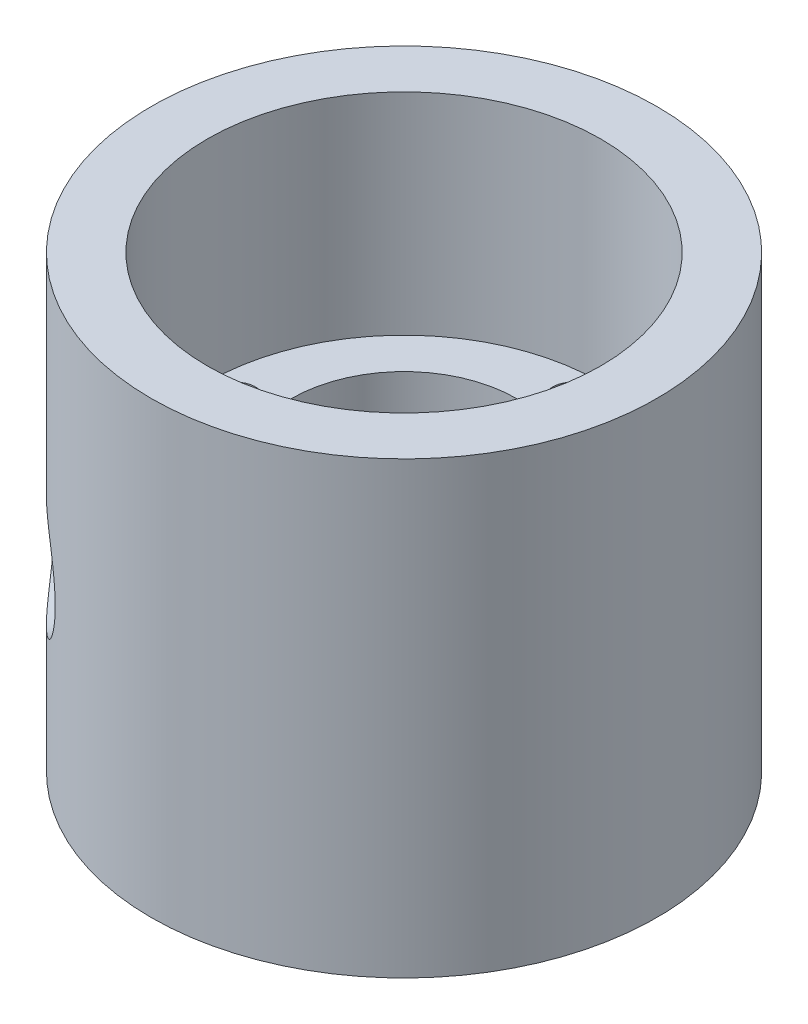
SolidWorks part; units mm, degrees
material "6061 Alloy"
ref_plane "Front Plane" through (0, 0, 0) normal (0, 0, 1) x (1, 0, 0)
ref_plane "Top Plane" through (0, 0, 0) normal (0, 1, 0) x (1, 0, 0)
ref_plane "Right Plane" through (0, 0, 0) normal (1, 0, 0) x (0, 0, -1)
sketch "Sketch1" plane through (0, 0, 0) normal (0, 1, 0) x (1, 0, 0)
  circle A1 centre (0, 0) radius 14.2875
  dimension "D2" = 28.575
extrude "Boss-Extrude1" add sketch "Sketch1" along normal blind 25.4
sketch "Sketch3" plane through (0, 0, 0) normal (0, -1, 0) x (1, 0, 0)
  circle A0 centre (0, 0) radius 11.1125
  dimension "D1" = 22.225
extrude "Cut-Extrude1" cut sketch "Sketch3" against normal blind 7.1437
sketch "Sketch4" plane through (0, 25.4, 0) normal (0, 1, 0) x (1, 0, 0)
  line L1 (-1.5875, 7.9375) -> (1.5875, 7.9375)
  line L2 (-7.9375, 1.5875) -> (-7.9375, -1.5875)
  line L3 (-1.5875, -7.9375) -> (1.5875, -7.9375)
  line L4 (7.9375, 1.5875) -> (7.9375, -1.5875)
  arc A0 (1.5875, -7.9375) -> (7.9375, -1.5875) centre (1.5875, -1.5875) ccw
  arc A1 (1.5875, 7.9375) -> (7.9375, 1.5875) centre (1.5875, 1.5875) cw
  arc A2 (-7.9375, -1.5875) -> (-1.5875, -7.9375) centre (-1.5875, -1.5875) ccw
  arc A3 (-1.5875, 7.9375) -> (-7.9375, 1.5875) centre (-1.5875, 1.5875) ccw
  point P6 (7.9375, -7.9375)
  point P9 (7.9375, 7.9375)
  point P14 (-7.9375, 7.9375)
  dimension "D3" = 6.35
  dimension "D1" = 15.875
  dimension "D2" = 15.875
  dimension "D4" = 7.9375
  dimension "D5" = 7.9375
extrude "Cut-Extrude2" cut sketch "Sketch4" against normal blind 18.2562
sketch "Sketch5" plane through (0, 25.4, 0) normal (0, 1, 0) x (1, 0, 0)
  circle A0 centre (0, 0) radius 11.1125
  dimension "D1" = 22.225
extrude "Cut-Extrude3" cut sketch "Sketch5" against normal blind 11.9062
hole_wizard "#4-40 Tapped Hole1" positions "Sketch7" profile "Sketch6" tap size "#4-40" standard "Ansi Inch" end condition through all
sketch "Sketch7" plane through (0, 13.4937, 0) normal (0, 1, 0) x (-1, 0, 0)
  point P0 (0, -9.525)
  dimension "D1" = 9.525
sketch "Sketch6" plane through (0, 13.4937, -9.525) normal (1, 0, 0) x (0, 0, 1)
  line L0 (0, 0) -> (0, 13.4937)
  line L1 (0, 13.4937) -> (1.1303, 13.4937)
  line L2 (1.1303, 13.4937) -> (1.1303, 0)
  line L5 (1.1303, 0) -> (0, 0)
  line L11 (0, -6.35) -> (0, 107.95) construction
  dimension "Thread Major Dia." = 2.2606
  dimension "Thru Tap Drill Depth" = 13.4937
pattern_circular "CirPattern1" count 4 over 360 about axis through (0, 25.4, 0) along (0, 1, 0) of "#4-40 Tapped Hole1"
ref_axis "Axis1" through (0, 13.4937, 0) along (0, 1, 0)
ref_plane "Plane1" through (0, 0, 0) normal (0.7071, 0, -0.7071) x (-0.7071, 0, -0.7071)
sketch "Sketch8" plane through (0, 0, 0) normal (0.7071, 0, -0.7071) x (-0.7071, 0, -0.7071)
  line L0 (0, 13.4937) -> (0, 25.4) construction
  line L1 (-14.2875, 0) -> (14.2875, 0) construction
  circle A0 centre (0, 10.3187) radius 3.1496
  dimension "D1" = 6.2992
  dimension "D2" = 10.3187
extrude "Cut-Extrude6" cut sketch "Sketch8" against normal through all
